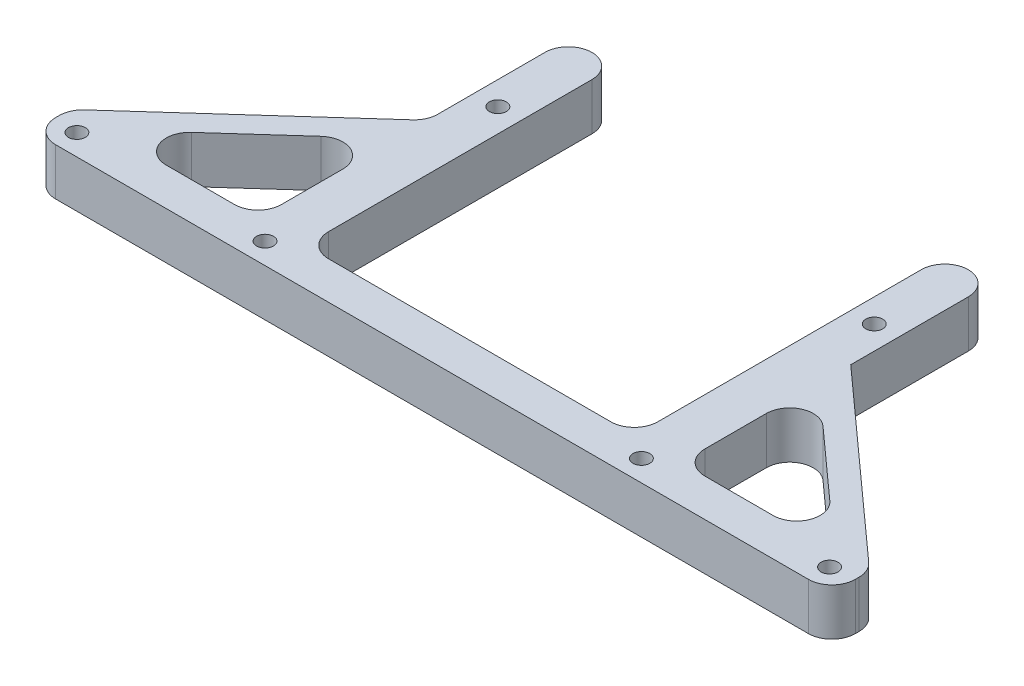
SolidWorks part; units mm, degrees
ref_plane "Front Plane" through (0, 0, 0) normal (0, 0, 1) x (1, 0, 0)
ref_plane "Top Plane" through (0, 0, 0) normal (0, 1, 0) x (1, 0, 0)
ref_plane "Right Plane" through (0, 0, 0) normal (1, 0, 0) x (0, 0, -1)
sketch "Sketch2" plane through (0, 0, 0) normal (0, 1, 0) x (1, 0, 0)
  line L0 (0, 0) -> (0, 10.16) construction
  line L1 (107.95, 0) -> (-107.95, 0)
  line L2 (-107.95, 0) -> (-107.95, 10.16)
  line L3 (-107.95, 10.16) -> (-57.15, 55.88)
  line L4 (-57.15, 55.88) -> (-57.15, 93.98)
  line L5 (-57.15, 93.98) -> (-44.45, 93.98)
  line L6 (-44.45, 93.98) -> (-44.45, 10.16)
  line L7 (-44.45, 10.16) -> (44.45, 10.16)
  line L8 (-57.15, 10.16) -> (-98.4577, 10.16)
  line L9 (-98.4577, 10.16) -> (-57.15, 47.3369)
  line L10 (-57.15, 47.3369) -> (-57.15, 10.16)
  line L11 (57.15, 93.98) -> (44.45, 93.98)
  line L12 (57.15, 55.88) -> (57.15, 93.98)
  line L13 (44.45, 93.98) -> (44.45, 10.16)
  line L14 (57.15, 47.3369) -> (57.15, 10.16)
  line L15 (57.15, 10.16) -> (98.4577, 10.16)
  line L16 (98.4577, 10.16) -> (57.15, 47.3369)
  line L17 (107.95, 10.16) -> (57.15, 55.88)
  line L18 (107.95, 0) -> (107.95, 10.16)
  circle A0 centre (-50.8, 68.58) radius 2.286
  circle A1 centre (50.8, 68.58) radius 2.286
  circle A2 centre (-101.6, 5.715) radius 2.286
  circle A3 centre (-50.8, 5.715) radius 2.286
  circle A4 centre (101.6, 5.715) radius 2.286
  circle A5 centre (50.8, 5.715) radius 2.286
  point P6 (-50.8, 93.98)
  point P14 (0, 5.08)
  dimension "D6" = 4.572
  dimension "D12" = 4.572
  dimension "D1" = 10.16
  dimension "D2" = 12.7
  dimension "D3" = 50.8
  dimension "D4" = 107.95
  dimension "D5" = 25.4
  dimension "D7" = 63.5
  dimension "D8" = 12.7
  dimension "D9" = 6.35
  dimension "D10" = 5.715
  dimension "D11" = 6.35
  dimension "D13" = 50.8
extrude "Boss-Extrude1" add sketch "Sketch2" along normal blind 12.7
fillet "Fillet1" radius 6.35 17 edges at (57.15, 6.35, -93.98) (44.45, 6.35, -93.98) (-44.45, 6.35, -93.98) (-57.15, 6.35, -93.98) (-107.95, 6.35, -10.16) (-107.95, 6.35, 0) (107.95, 6.35, -10.16) (107.95, 6.35, 0) (98.4577, 6.35, -10.16) (57.15, 6.35, -47.3369) (57.15, 6.35, -10.16) (44.45, 6.35, -10.16) (-44.45, 6.35, -10.16) (-57.15, 6.35, -10.16) (-98.4577, 6.35, -10.16) (-57.15, 6.35, -47.3369) (-57.15, 6.35, -55.88)
